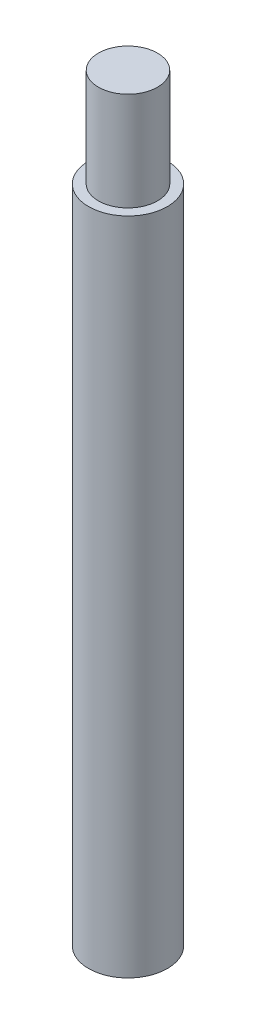
SolidWorks part; units mm, degrees
ref_plane "Спереди" through (0, 0, 0) normal (0, 0, 1) x (1, 0, 0)
ref_plane "Сверху" through (0, 0, 0) normal (0, 1, 0) x (1, 0, 0)
ref_plane "Справа" through (0, 0, 0) normal (1, 0, 0) x (0, 0, -1)
sketch "Эскиз1" plane through (0, 0, 0) normal (0, 1, 0) x (1, 0, 0)
  circle A0 centre (0, 0) radius 8
extrude "Вытянуть1" add sketch "Эскиз1" along normal blind 154 from offset 65
sketch "Эскиз2" plane through (0, 219, 0) normal (0, 1, 0) x (1, 0, 0)
  circle A0 centre (0, 0) radius 6
  circle A1 centre (0, 0) radius 10
extrude "Вырез-Вытянуть1" cut sketch "Эскиз2" against normal blind 20
sketch "Эскиз3" plane through (0, 65, 0) normal (0, -1, 0) x (1, 0, 0)
  circle A0 centre (0, 0) radius 8
curve "Спираль1" pitch 2 height 260 turns 130
sketch "Эскиз4" plane through (0, 0, 0) normal (1, 0, 0) x (0, 0, -1)
  line L0 (-8.1796, -0.1941) -> (-8.1796, -1.3022)
  line L1 (-8.1796, -1.3022) -> (-6.9709, -0.7482)
  line L2 (-6.9709, -0.7482) -> (-8.1796, -0.1941)
sweep "Вырез-По траектории1" [suppressed] cut profiles "Эскиз4" path "Спираль1"
